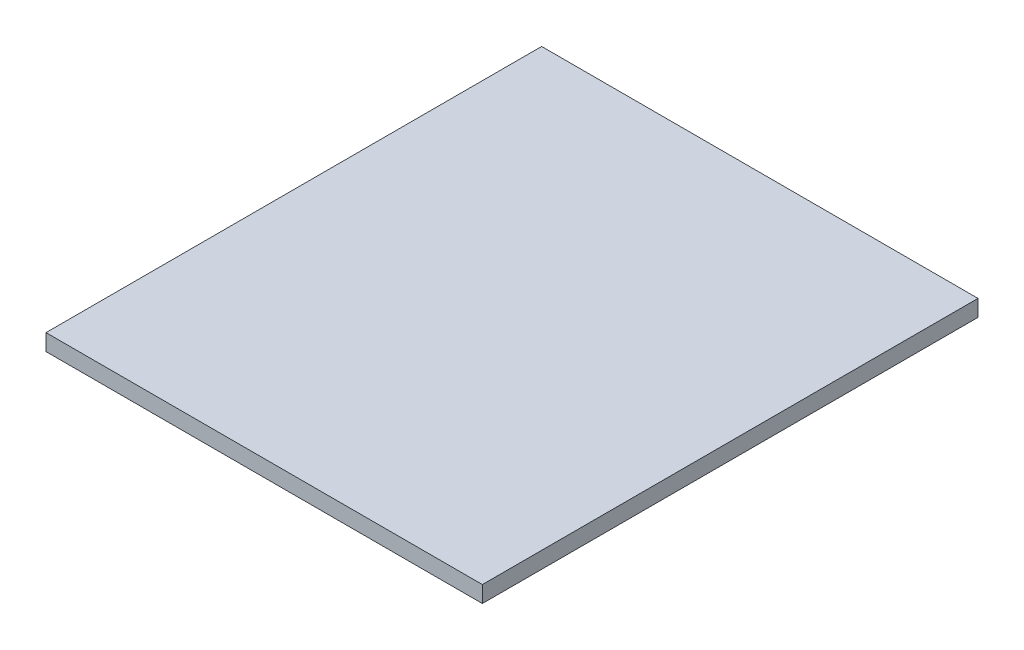
SolidWorks part; units mm, degrees
ref_plane "Front Plane" through (0, 0, 0) normal (0, 0, 1) x (1, 0, 0)
ref_plane "Top Plane" through (0, 0, 0) normal (0, 1, 0) x (1, 0, 0)
ref_plane "Right Plane" through (0, 0, 0) normal (1, 0, 0) x (0, 0, -1)
sketch "Sketch1" plane through (0, 0, 0) normal (0, 1, 0) x (1, 0, 0)
  line L1 (0, 0) -> (26.5, 0)
  line L2 (0, 0) -> (0, 30.1)
  line L3 (0, 30.1) -> (26.5, 30.1)
  line L4 (26.5, 0) -> (26.5, 30.1)
  dimension "D1" = 26.5
  dimension "D2" = 30.1
extrude "Boss-Extrude1" add sketch "Sketch1" along normal blind 1
